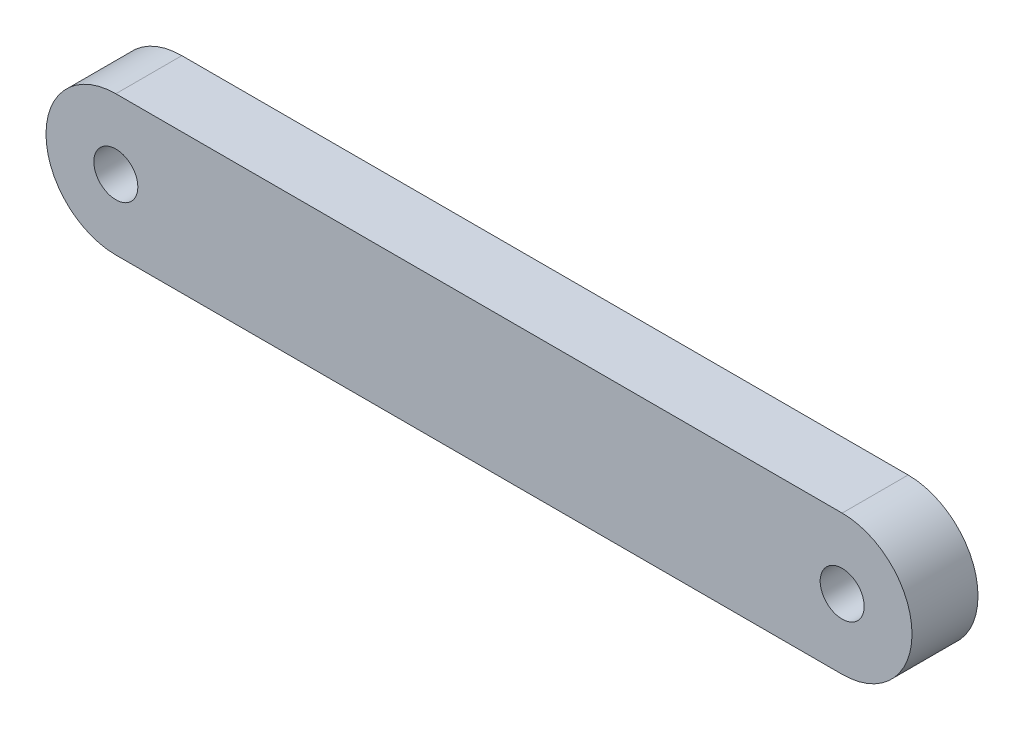
SolidWorks part; units mm, degrees
ref_plane "Front Plane" through (0, 0, 0) normal (0, 0, 1) x (1, 0, 0)
ref_plane "Top Plane" through (0, 0, 0) normal (0, 1, 0) x (1, 0, 0)
ref_plane "Right Plane" through (0, 0, 0) normal (1, 0, 0) x (0, 0, -1)
sketch "Sketch2" plane through (0, 0, 0) normal (0, 0, 1) x (1, 0, 0)
  line L0 (0, 0) -> (33.02, 0)
  dimension "D1" = 33.02
extrude "Extrude-Thin1" add sketch "Sketch2" along normal blind 3 thin thin type mid plane wall 6.35
sketch "Sketch3" plane through (0, 0, 3) normal (0, 0, 1) x (1, 0, 0)
  line L0 (33.02, 3.175) -> (33.02, -3.175) construction
  circle A0 centre (0, 0) radius 3.175
  circle A1 centre (33.02, 0) radius 3.175
  circle A2 centre (0, 0) radius 1
  circle A3 centre (33.02, 0) radius 1
  line M3 (33.02, -3.175) -> (33.02, 3.175)
  line M5 (0, 3.175) -> (0, -3.175)
  dimension "D1" = 2
extrude "Boss-Extrude1" add sketch "Sketch3" against normal through all
extrude "Cut-Extrude1" cut sketch "Sketch3<2>" against normal through all contours A2 M5 | A3 M3 region at (0.4244, 0, 3) region at (32.5956, 0, 3)
sketch "Sketch3<2>" plane through (0, 0, 3) normal (0, 0, 1) x (1, 0, 0) same geometry as "Sketch3"
equation "\"member length\"= 1.3"
equation "\"member width\"= 1 / 4"
equation "\"member thickness\"= 3mm"
equation "\"D1@Sketch2\"=\"member length\""
equation "\"D5@Extrude-Thin1\"=\"member width\""
equation "\"D1@Extrude-Thin1\"=\"member thickness\""
equation "\"hole size\"= 2mm"
equation "\"D1@Sketch3\"=\"hole size\""
